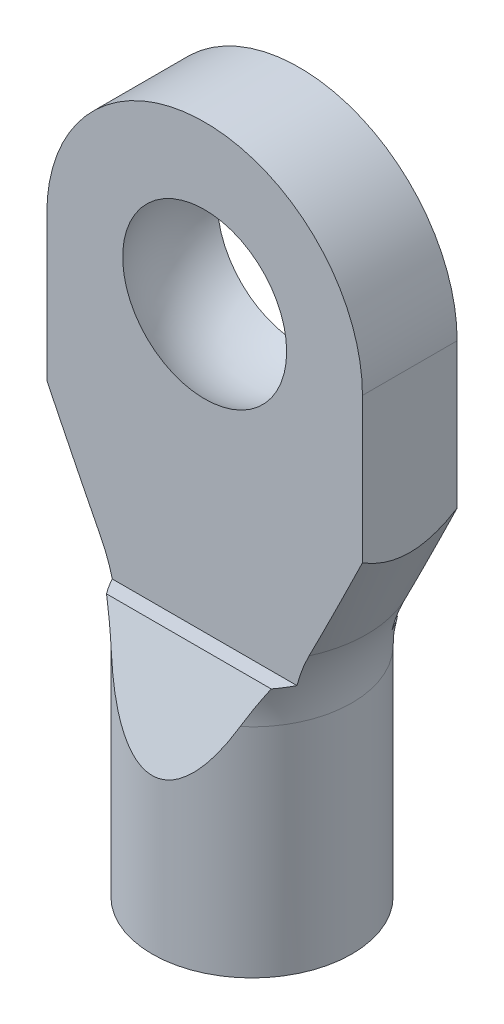
SolidWorks part; units mm, degrees
ref_plane "Front Plane" through (0, 0, 0) normal (0, 0, 1) x (1, 0, 0)
ref_plane "Top Plane" through (0, 0, 0) normal (0, 1, 0) x (1, 0, 0)
ref_plane "Right Plane" through (0, 0, 0) normal (1, 0, 0) x (0, 0, -1)
sketch "Sketch1" plane through (0, 0, 0) normal (0, 0, 1) x (1, 0, 0)
  line L0 (0, 0) -> (0, 22) construction
  line L1 (-3.5, 8.5) -> (-3.5, 0)
  line L2 (5, 17) -> (5, 11.8)
  line L3 (5, 11.8) -> (3.5, 8.5)
  line L4 (3.5, 8.5) -> (3.5, 0)
  line L5 (3.5, 0) -> (-3.5, 0)
  line L6 (-5, 11.8) -> (-3.5, 8.5)
  line L7 (-5, 17) -> (-5, 11.8)
  arc A0 (5, 17) -> (-5, 17) centre (0, 17) ccw
  dimension "D2" = 10
  dimension "D1" = 17
  dimension "D3" = 8.5
  dimension "D4" = 3.3
  dimension "D5" = 3.5
extrude "Boss-Extrude1" add sketch "Sketch1" along normal blind 1.5 and the other way blind 1.5
sketch "Sketch3" plane through (0, 0, 0) normal (0, 1, 0) x (1, 0, 0)
  circle A0 centre (0, 0) radius 3.5
  dimension "D1" = 7
extrude "Boss-Extrude2" add sketch "Sketch3" along normal blind 8
sketch "Sketch5" plane through (0, 0, 0) normal (1, 0, 0) x (0, 0, -1)
  line L0 (0, 0) -> (0, 8.5) construction
  line L1 (-1.5, 0) -> (1.5, 0) construction
  line L2 (-1.5, 8.5) -> (1.5, 8.5) construction
  line L3 (2, 8) -> (3.5, 4)
  line L4 (3.5, 8) -> (1.5, 8) construction
  line L5 (3.5, 0) -> (3.5, 8) construction
  line L6 (3.5, 4) -> (3.5, 8)
  line L7 (3.5, 8) -> (2, 8)
  line L8 (-3.5, 8) -> (-2, 8)
  line L9 (-3.5, 4) -> (-3.5, 8)
  line L10 (-2, 8) -> (-3.5, 4)
  dimension "D1" = 1.5
  dimension "D2" = 4
extrude "Cut-Extrude2" cut sketch "Sketch5" against normal through all and the other way through all
sketch "Sketch6" plane through (0, 0, 0) normal (0, 0, 1) x (1, 0, 0)
  line L0 (7.3636, 17) -> (3.6316, 9.0054)
  line L1 (3.1623, 6.8904) -> (3.1623, 0)
  line L2 (3.1623, 0) -> (7.3636, 0)
  line L3 (7.3636, 0) -> (7.3636, 17)
  line L4 (0, 0) -> (0, 8) construction
  line L5 (3.1623, 8) -> (-3.1623, 8) construction
  line L8 (3.5, 8.5) -> (5, 11.8) construction
  arc A0 (3.1623, 6.8904) -> (3.6316, 9.0054) centre (8.1623, 6.8904) cw
  point P14 (3.1623, 8)
  dimension "D1" = 5
  dimension "D2" = 17
revolve "Cut-Revolve1" cut sketch "Sketch6" angle 360 about L4
sketch "Sketch7" plane through (0, 0, 0) normal (0, 0, 1) x (1, 0, 0)
  line L0 (0, 20) -> (0, 14)
  line L1 (0, 0) -> (0, 14) construction
  arc A0 (0, 14) -> (0, 20) centre (0, 17) ccw
  dimension "D2" = 6
  dimension "D1" = 17
revolve "Cut-Revolve2" cut sketch "Sketch7" angle 360 about L1
sketch "Sketch8" plane through (0, 0, 0) normal (0, -1, 0) x (1, 0, 0)
  circle A0 centre (0, 0) radius 1.75
  dimension "D1" = 3.5
extrude "Cut-Extrude3" cut sketch "Sketch8" against normal blind 5
